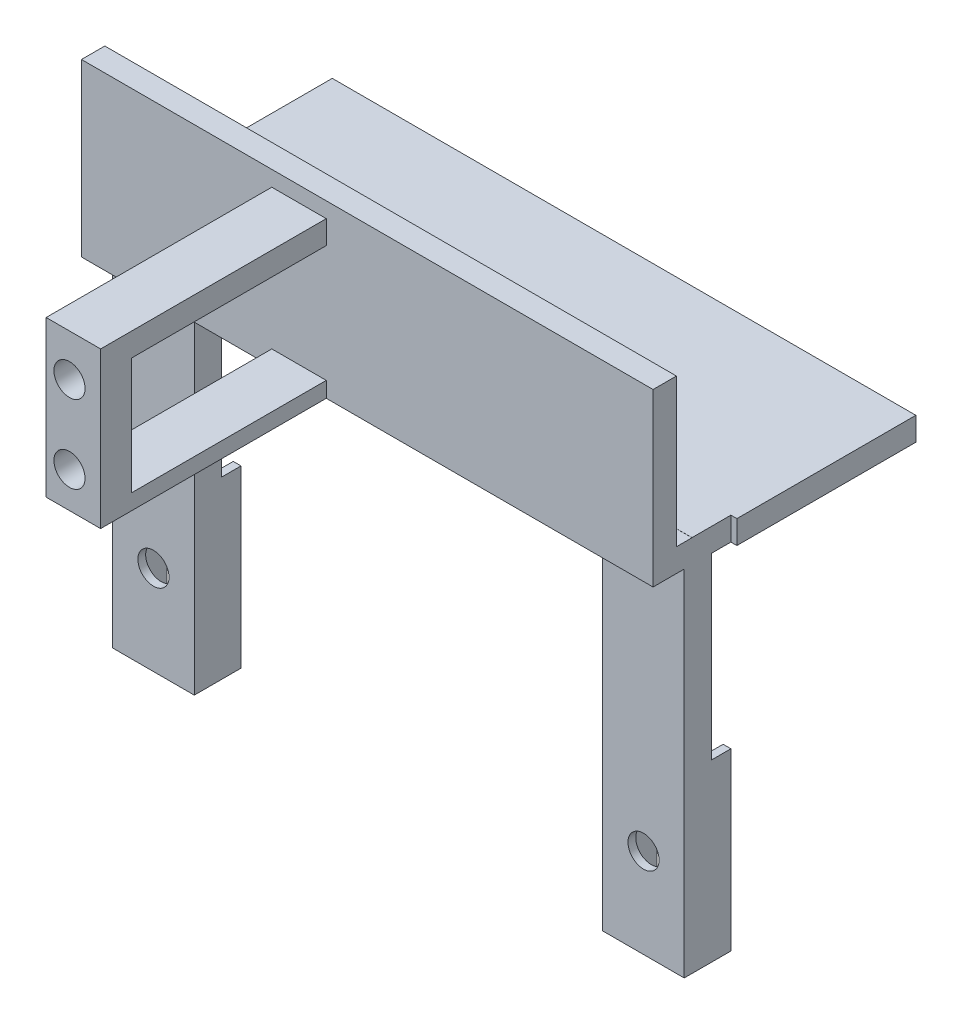
SolidWorks part; units mm, degrees
ref_plane "Front Plane" through (0, 0, 0) normal (0, 0, 1) x (1, 0, 0)
ref_plane "Top Plane" through (0, 0, 0) normal (0, 1, 0) x (1, 0, 0)
ref_plane "Right Plane" through (0, 0, 0) normal (1, 0, 0) x (0, 0, -1)
sketch "Sketch1" plane through (0, 0, 0) normal (0, 1, 0) x (1, 0, 0)
  line L1 (-37.5, -11.5) -> (37.5, -11.5)
  line L2 (-37.5, -11.5) -> (-37.5, 11.5)
  line L3 (-37.5, 11.5) -> (37.5, 11.5)
  line L4 (37.5, -11.5) -> (37.5, 11.5)
  line L5 (-37.5, -11.5) -> (37.5, 11.5) construction
  line L6 (-37.5, 11.5) -> (37.5, -11.5) construction
  point P0 (0, 0)
extrude "Boss-Extrude1" add sketch "Sketch1" along normal blind 3
sketch "Sketch2" plane through (0, 0, 11.5) normal (0, 0, 1) x (1, 0, 0)
  line L3 (27.2303, 0) -> (27.2303, -45.5149)
  line L5 (-35.4803, -45.5149) -> (-37.4966, -45.5149) construction
  line L7 (-12.4738, -45.5149) -> (-27.4803, -45.5149) construction
  line L14 (-35.7303, -45.5149) -> (-36.7303, -45.5149)
  line L15 (-27.2303, -45.5149) -> (-26.2303, -45.5149)
  line L16 (-26.2303, -45.5149) -> (-26.2303, 3)
  line L17 (-37.5, 3) -> (37.5, 3) construction
  line L19 (-26.2303, 3) -> (-36.7303, 3)
  line L20 (-36.7303, 3) -> (-36.7303, -45.5149)
  line L22 (-35.7303, -45.5149) -> (-35.7303, 0)
  line L23 (-37.5, 0) -> (37.5, 0) construction
  line L24 (-35.7303, 0) -> (-27.2303, 0)
  line L25 (-27.2303, 0) -> (-27.2303, -45.5149)
  line L26 (35.7303, 0) -> (27.2303, 0)
  line L27 (35.7303, -45.5149) -> (35.7303, 0)
  line L28 (36.7303, 3) -> (36.7303, -45.5149)
  line L29 (26.2303, 3) -> (36.7303, 3)
  line L30 (26.2303, -45.5149) -> (26.2303, 3)
  line L31 (27.2303, -45.5149) -> (26.2303, -45.5149)
  line L32 (35.7303, -45.5149) -> (36.7303, -45.5149)
extrude "Boss-Extrude4" add sketch "Sketch2" along normal blind 5
sketch "Sketch3" plane through (0, -45.5149, 0) normal (0, -1, 0) x (1, 0, 0)
  line L0 (-36.7303, 16.5) -> (-26.2303, 16.5)
  line L1 (-26.2303, 16.5) -> (-26.2303, 17.5)
  line L2 (-26.2303, 17.5) -> (-36.7303, 17.5)
  line L3 (-36.7303, 17.5) -> (-36.7303, 16.5)
  line L4 (26.2303, 16.5) -> (36.7303, 16.5)
  line L5 (36.7303, 16.5) -> (36.7303, 17.5)
  line L6 (36.7303, 17.5) -> (26.2303, 17.5)
  line L7 (26.2303, 17.5) -> (26.2303, 16.5)
extrude "Boss-Extrude5" add sketch "Sketch3" against normal blind 48.5
sketch "Sketch4" plane through (0, 0, 16.5) normal (0, 0, -1) x (-1, 0, 0)
  circle A0 centre (31.4813, -34.0121) radius 2
  circle A1 centre (-31.5034, -34.0149) radius 2
extrude "Cut-Extrude1" cut sketch "Sketch4" against normal through all
sketch "Sketch8" plane through (0, 0, 11.5) normal (0, 0, 1) x (1, 0, 0)
  line L1 (-36.7303, 2.9851) -> (36.7303, 2.9851)
  line L2 (-36.7303, 2.9851) -> (-36.7303, 0)
  line L3 (-36.7303, 0) -> (36.7303, 0)
  line L4 (36.7303, 2.9851) -> (36.7303, 0)
extrude "Boss-Extrude9" add sketch "Sketch8" along normal blind 10
sketch "Sketch12" plane through (0, 2.9851, 0) normal (0, 1, 0) x (1, 0, 0)
  line L0 (36.7303, -18.5) -> (47.827, -18.5) construction
  line L1 (36.7303, -16.5) -> (36.7303, -21.5) construction
  line L2 (47.827, -18.5) -> (-50.2663, -18.5) construction
  line L3 (36.7303, -21.5) -> (-36.7303, -21.5) construction
  line L5 (-36.7303, -21.5) -> (36.7303, -21.5)
  line L6 (-36.7303, -21.5) -> (-36.7303, -18.5)
  line L7 (-36.7303, -18.5) -> (36.7303, -18.5)
  line L8 (36.7303, -21.5) -> (36.7303, -18.5)
  dimension "D1" = 3
extrude "Boss-Extrude10" add sketch "Sketch12" along normal blind 19
sketch "Sketch13" plane through (0, 0, 21.5) normal (0, 0, 1) x (1, 0, 0)
  line L0 (-36.7303, 0) -> (36.7303, 0) construction
  line L1 (-12.2697, 0) -> (-5.2697, 0)
  line L2 (-12.2697, 0) -> (-12.2697, 20)
  line L3 (-12.2697, 20) -> (-5.2697, 20)
  line L4 (-5.2697, 0) -> (-5.2697, 20)
  line L5 (36.7303, 0) -> (36.7303, 21.9851) construction
  dimension "D1" = 42
  dimension "D2" = 20
  dimension "D3" = 7
extrude "Boss-Extrude11" add sketch "Sketch13" along normal blind 29
sketch "Sketch14" plane through (0, 0, 50.5) normal (0, 0, 1) x (1, 0, 0)
  line L0 (-9.2697, 20) -> (-9.2697, 25.7375) construction
  line L1 (-5.2697, 20) -> (-12.2697, 20) construction
  line L2 (-9.2697, 25.7375) -> (-9.2697, -6.6243) construction
  line L3 (-5.2697, 0) -> (-5.2697, 20) construction
  line L4 (-5.2697, 20) -> (-12.2697, 20) construction
  line L5 (-12.2697, 0) -> (-5.2697, 0) construction
  circle A0 centre (-9.2697, 14.59) radius 2
  circle A1 centre (-9.2697, 4.59) radius 2
  dimension "D2" = 4
  dimension "D3" = 4
  dimension "D1" = 4
  dimension "D4" = 5.41
  dimension "D5" = 4.59
extrude "Cut-Extrude2" cut sketch "Sketch14" against normal blind 10
sketch "Sketch15" plane through (-36.7303, 0, 0) normal (-1, 0, 0) x (0, 0, 1)
  line L1 (11.5, 0) -> (14, 0)
  line L2 (11.5, 0) -> (11.5, -23)
  line L3 (11.5, -23) -> (14, -23)
  line L4 (14, 0) -> (14, -23)
  dimension "D1" = 2.5
  dimension "D2" = 23
extrude "Cut-Extrude3" cut sketch "Sketch15" against normal through all
sketch "Sketch17" plane through (-12.2697, 0, 0) normal (-1, 0, 0) x (0, 0, 1)
  line L0 (21.5, 20) -> (21.5, 0) construction
  line L1 (21.5, 17) -> (46.5, 17)
  line L2 (21.5, 17) -> (21.5, 2)
  line L3 (21.5, 2) -> (46.5, 2)
  line L4 (46.5, 17) -> (46.5, 2)
  line L5 (50.5, 0) -> (21.5, 0) construction
  line L6 (50.5, 20) -> (21.5, 20) construction
  line L7 (50.5, 20) -> (50.5, 0) construction
  dimension "D1" = 2
  dimension "D2" = 3
  dimension "D3" = 4
extrude "Cut-Extrude4" cut sketch "Sketch17" against normal through all
ref_plane "Plane5" through (26.2303, 0, 17.5) normal (-1, 0, 0) x (0, 0, 1)
